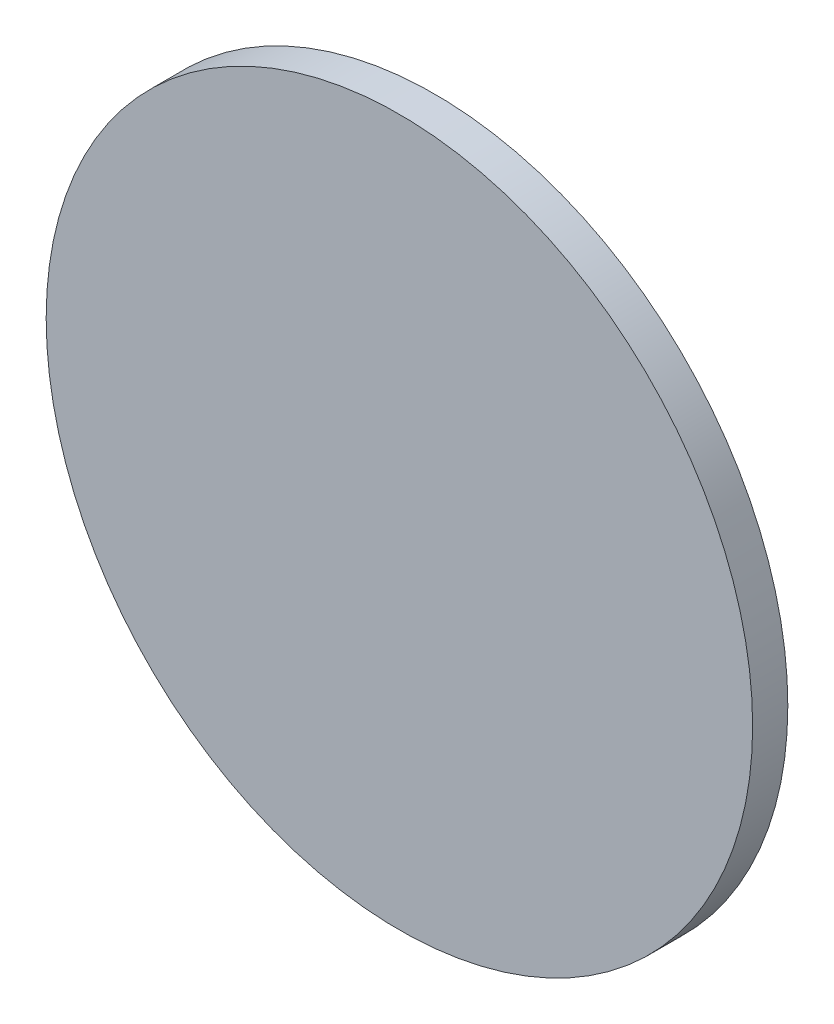
SolidWorks part; units mm, degrees
ref_plane "Front Plane" through (0, 0, 0) normal (0, 0, 1) x (1, 0, 0)
ref_plane "Top Plane" through (0, 0, 0) normal (0, 1, 0) x (1, 0, 0)
ref_plane "Right Plane" through (0, 0, 0) normal (1, 0, 0) x (0, 0, -1)
sketch "Sketch1" plane through (0, 0, 0) normal (0, 0, 1) x (1, 0, 0)
  circle A0 centre (0, 0) radius 63.76
extrude "Boss-Extrude1" add sketch "Sketch1" along normal blind 6.35
sketch "Sketch4" plane through (0, 0, 0) normal (0, 0, -1) x (-1, 0, 0)
  line L1 (-12.4, 32.91) -> (12.4, 32.91)
  line L2 (-12.4, 32.91) -> (-12.4, -12.42)
  line L3 (-12.4, -12.42) -> (12.4, -12.42)
  line L4 (12.4, 32.91) -> (12.4, -12.42)
  dimension "D1" = 12.42
  dimension "D2" = 32.91
  dimension "D3" = 12.4
  dimension "D4" = 12.4
extrude "Cut-Extrude1" cut sketch "Sketch4" against normal blind 5
fillet "Fillet1" radius 6.35 4 edges at (12.4, 32.91, 2.5) (-12.4, 32.91, 2.5) (12.4, -12.42, 2.5) (-12.4, -12.42, 2.5)
